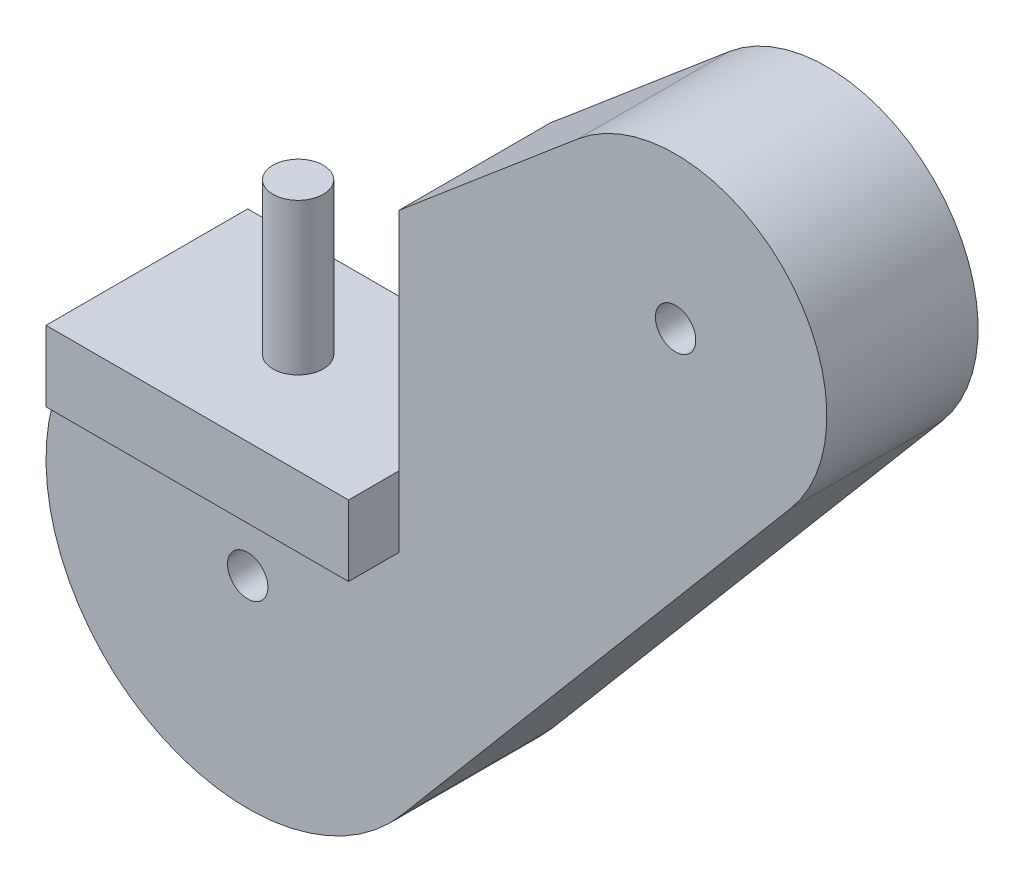
SolidWorks part; units mm, degrees
ref_plane "Front Plane" through (0, 0, 0) normal (0, 0, 1) x (1, 0, 0)
ref_plane "Top Plane" through (0, 0, 0) normal (0, 1, 0) x (1, 0, 0)
ref_plane "Right Plane" through (0, 0, 0) normal (1, 0, 0) x (0, 0, -1)
ref_axis "Axis1" through (-23.7295, 0, 0) along (1, 0, 0)
sketch "Sketch1" plane through (0, 0, 0) normal (0, 0, 1) x (1, 0, 0)
  line L0 (-12.9144, 15.2715) -> (32.7406, 53.88)
  line L1 (53.88, 32.7406) -> (15.2715, -12.9144)
  line L2 (0, 0) -> (42.4264, 42.4264) construction
  line L3 (-23.7295, 0) -> (58.3201, 0) construction
  arc A0 (-12.9144, 15.2715) -> (15.2715, -12.9144) centre (0, 0) ccw
  arc A1 (32.7406, 53.88) -> (53.88, 32.7406) centre (42.4264, 42.4264) cw
  point P1 (26.2871, 57.3061)
  point P9 (0, 0)
  point P12 (50.9935, 30.1136)
  dimension "D1" = 20
  dimension "D2" = 15
  dimension "D3" = 60
  dimension "D4" = 45
extrude "Boss-Extrude1" add sketch "Sketch1" along normal blind 15
sketch "Sketch2" plane through (0, 0, 15) normal (0, 0, 1) x (1, 0, 0)
  circle A0 centre (0, 0) radius 2
  circle A1 centre (42.4264, 42.4264) radius 2
  arc A2 (53.88, 32.7406) -> (32.7406, 53.88) centre (42.4264, 42.4264) ccw construction
  dimension "D1" = 4
  dimension "D2" = 4
extrude "Cut-Extrude1" cut sketch "Sketch2" against normal through all both
sketch "Sketch3" plane through (0, 0, 15) normal (0, 0, 1) x (1, 0, 0)
  line L0 (-23.7295, 0) -> (58.3201, 0) construction
  line L1 (-15, 9.5) -> (15, 9.5)
  line L2 (-15, 9.5) -> (-15, 16.5)
  line L3 (-15, 16.5) -> (15, 16.5)
  line L4 (15, 9.5) -> (15, 16.5)
  line L5 (-15, 9.5) -> (15, 16.5) construction
  line L6 (-15, 16.5) -> (15, 9.5) construction
  point P0 (0, 13)
  point P5 (0, 0)
  dimension "D1" = 30
  dimension "D2" = 7
  dimension "D3" = 13
extrude "Boss-Extrude2" add sketch "Sketch3" along normal blind 5 and the other way blind 15
sketch "Sketch4" plane through (0, 0, 15) normal (0, 0, 1) x (1, 0, 0)
  line L0 (15, 16.5) -> (15, 46.8971)
  line L1 (15, 16.5) -> (-23.2055, 16.5)
  line L2 (15, 46.8971) -> (-23.2055, 46.8971)
  line L3 (-23.2055, 16.5) -> (-23.2055, 46.8971)
extrude "Cut-Extrude2" cut sketch "Sketch4" against normal through all both
sketch "Sketch5" plane through (0, 16.5, 0) normal (0, 1, 0) x (1, 0, 0)
  line L0 (-23.7295, 0) -> (58.3201, 0) construction
  line L1 (15, 0) -> (15, -15) construction
  circle A0 centre (0, -10) radius 2.5
  dimension "D1" = 5
  dimension "D2" = 10
  dimension "D3" = 15
extrude "Boss-Extrude3" add sketch "Sketch5" along normal blind 15
